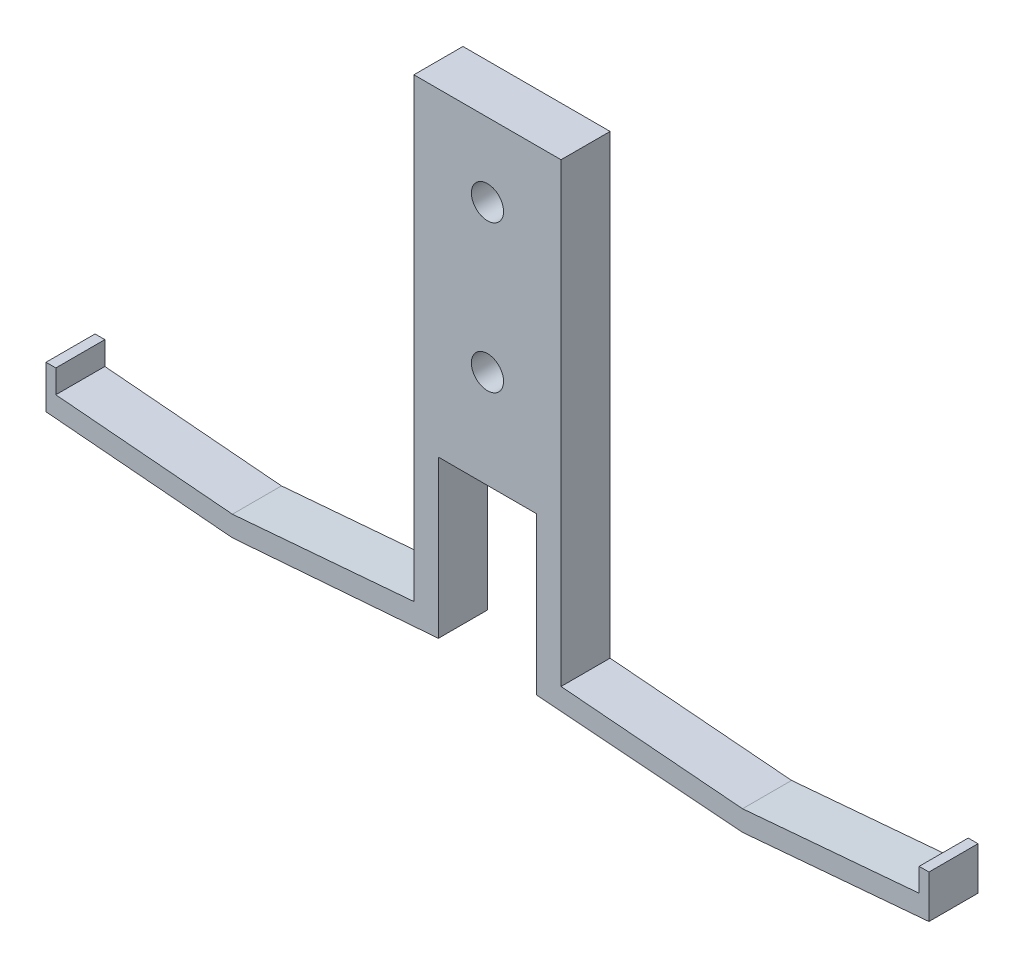
SolidWorks part; units mm, degrees
material "Nylon 6/10"
ref_plane "Front Plane" through (0, 0, 0) normal (0, 0, 1) x (1, 0, 0)
ref_plane "Top Plane" through (0, 0, 0) normal (0, 1, 0) x (1, 0, 0)
ref_plane "Right Plane" through (0, 0, 0) normal (1, 0, 0) x (0, 0, -1)
sketch "Sketch2" plane through (0, 0, 0) normal (0, 0, 1) x (1, 0, 0)
  line L1 (12.7, 0) -> (12.7, -40.64)
  line L2 (12.7, -40.64) -> (66.04, -44.7734)
  line L3 (66.04, -44.7734) -> (114.3, -40.64)
  line L4 (114.3, -40.64) -> (114.3, -29.5334)
  line L5 (111.76, -29.5334) -> (111.76, -35.56)
  line L6 (111.76, -35.56) -> (66.04, -39.4758)
  line L19 (114.3, -29.5334) -> (111.76, -29.5334)
  line L20 (0, 125.2351) -> (0, -75.9356) construction
  line L21 (12.7, 0) -> (-12.7, 0)
  line L22 (0, 0) -> (0, 82.55)
  line L23 (19.05, 82.55) -> (-19.05, 82.55)
  line L24 (19.05, 82.55) -> (19.05, 0)
  line L25 (19.05, 0) -> (19.05, -35.56)
  line L26 (19.05, -35.56) -> (66.04, -39.4758)
  line L27 (-19.05, 0) -> (-19.05, -35.56)
  line L28 (-19.05, 82.55) -> (-19.05, 0)
  line L29 (-12.7, 0) -> (-12.7, -40.64)
  line L30 (-12.7, -40.64) -> (-66.04, -44.7734)
  line L31 (-66.04, -44.7734) -> (-114.3, -40.64)
  line L32 (-114.3, -40.64) -> (-114.3, -29.5334)
  line L33 (-114.3, -29.5334) -> (-111.76, -29.5334)
  line L34 (-111.76, -29.5334) -> (-111.76, -35.56)
  line L35 (-111.76, -35.56) -> (-66.04, -39.4758)
  line L36 (-19.05, -35.56) -> (-66.04, -39.4758)
  dimension "D1" = 19.05
  dimension "D2" = 12.7
  dimension "D3" = 35.56
  dimension "D4" = 3.9158
  dimension "D5" = 40.64
  dimension "D6" = 2.54
  dimension "D7" = 45.72
  dimension "D8" = 46.99
  dimension "D9" = 15.24
  dimension "D10" = 82.55
extrude "Boss-Extrude1" add sketch "Sketch2" along normal blind 12.7 contours L26 L25 L24 L23 L22 L21 L1 L2 L3 L4 L19 L5 L6 | L27 L36 L35 L34 L33 L32 L31 L30 L29 L21 L22 L23 L28 region at (6.35, 1.711, 0) region at (-6.35, 1.711, 0)
hole_wizard "21/64 (0.32813) Diameter Hole1" positions "Sketch3" profile "Sketch4" hole size "21/64" standard "ANSI Inch" end condition through all
sketch "Sketch3" plane through (0, 0, 12.7) normal (0, 0, 1) x (1, 0, 0)
  point P0 (0, 25.4)
  point P2 (0, 63.5)
  dimension "D1" = 25.4
  dimension "D2" = 38.1
sketch "Sketch4" plane through (0, 25.4, 12.7) normal (1, 0, 0) x (0, -1, 0)
  line L0 (0, 0) -> (0, 12.7)
  line L1 (0, 12.7) -> (4.1673, 12.7)
  line L2 (4.1673, 12.7) -> (4.1673, 0)
  line L5 (4.1673, 0) -> (0, 0)
  line L11 (0, -6.35) -> (0, 107.95) construction
  dimension "Thru Hole Dia." = 8.3345
  dimension "Thru Hole Depth" = 12.7
